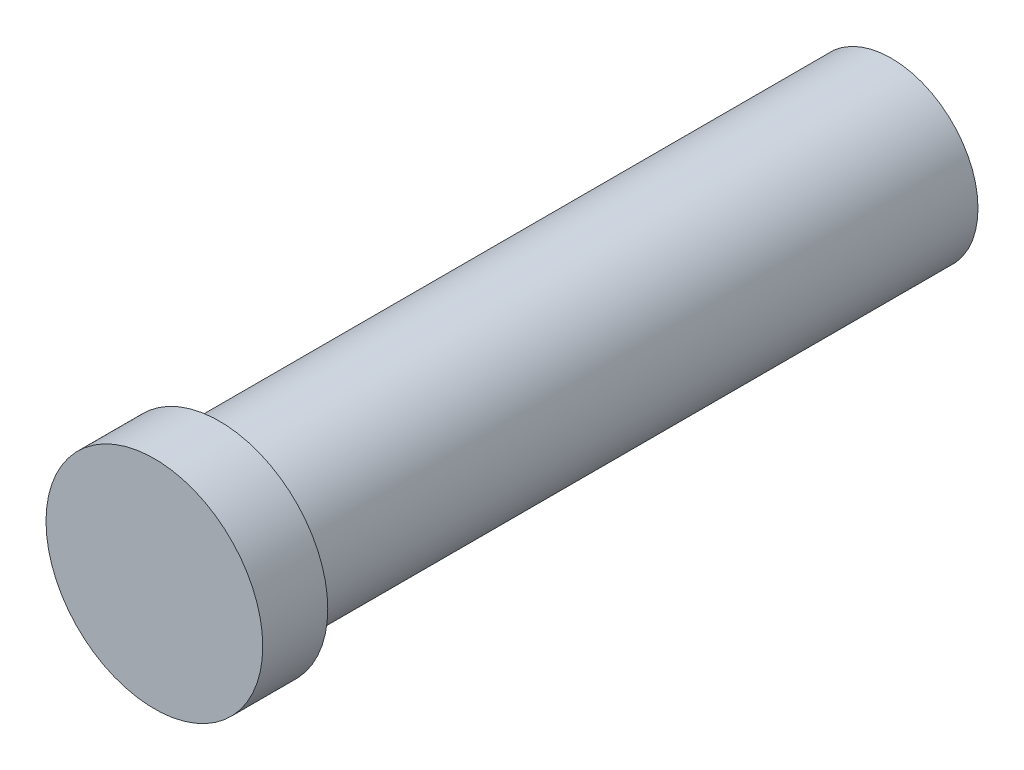
SolidWorks part; units mm, degrees
ref_plane "Ebene vorne" through (0, 0, 0) normal (0, 0, 1) x (1, 0, 0)
ref_plane "Ebene oben" through (0, 0, 0) normal (0, 1, 0) x (1, 0, 0)
ref_plane "Ebene rechts" through (0, 0, 0) normal (1, 0, 0) x (0, 0, -1)
sketch "Skizze1" plane through (0, 0, 0) normal (0, 0, 1) x (1, 0, 0)
  circle A0 centre (0, 0) radius 4
extrude "Aufsatz-Linear austragen1" add sketch "Skizze1" along normal blind 34
sketch "Skizze2" plane through (0, 0, 34) normal (0, 0, 1) x (1, 0, 0)
  circle A0 centre (0, 0) radius 5
extrude "Aufsatz-Linear austragen2" add sketch "Skizze2" against normal blind 3
sketch "Skizze3" plane through (0, 0, 0) normal (0, 0, -1) x (-1, 0, 0)
  circle A0 centre (0, 0) radius 2.25
  dimension "D1" = 4.5
extrude "Schnitt-Linear austragen1" cut sketch "Skizze3" against normal blind 18
thread "Gewinde1" pitch 0.8 method cut profile "Gewindeprofil1" start angle 0, offset 0, length 16, pitch 0.8, diameter 4.5
ref_plane "Ebene1" through (2.25, 0, 0) normal (0, -1, 0) x (1, 0, 0)
sketch "Gewindeprofil1" plane through (2.25, 0, 0) normal (0, -1, 0) x (1, 0, 0)
  line L0 (0, 0) -> (0, 0.8) construction
  line L1 (0, 0) -> (0.433, 0.25)
  line L2 (0.433, 0.25) -> (0.433, 0.35)
  line L3 (0.433, 0.35) -> (0, 0.6)
  line L4 (0.433, 0.3) -> (0, 0.3) construction
  line L11 (0, 0) -> (0, 0.6)
  point P2 (0, 0)
  dimension "Pitch" = 0.8
  dimension "Profile_Angle" = 60
  dimension "Profile_Land" = 0.1
  dimension "Profile_Height" = 0.433
